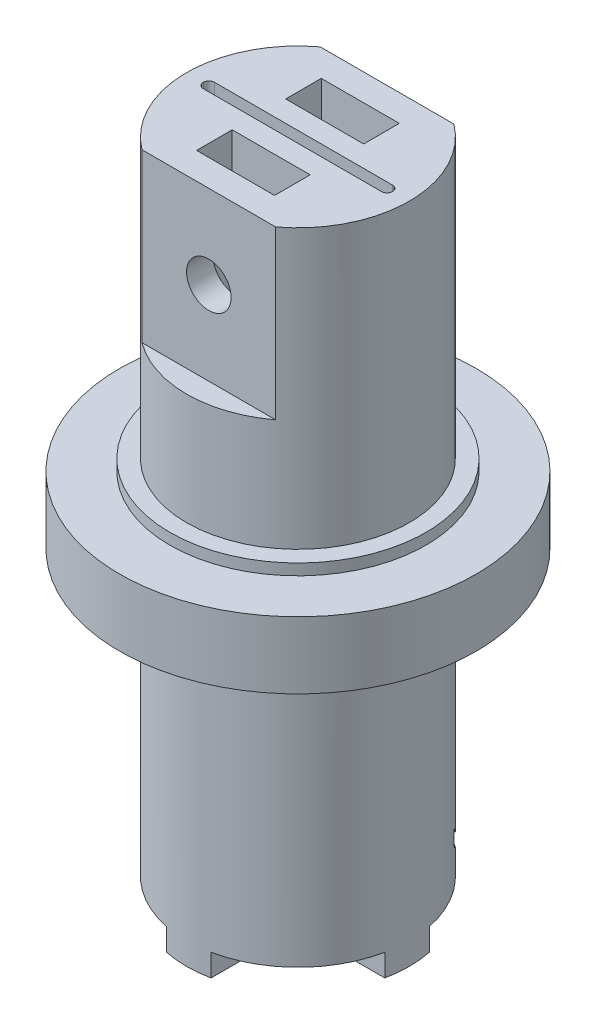
SolidWorks part; units mm, degrees
other "标注1"
sketch "草图8"
ref_plane "前视基准面" through (0, 0, 0) normal (0, 0, 1) x (1, 0, 0)
ref_plane "上视基准面" through (0, 0, 0) normal (0, 1, 0) x (1, 0, 0)
ref_plane "右视基准面" through (0, 0, 0) normal (1, 0, 0) x (0, 0, -1)
sketch "草图1" plane through (0, 0, 0) normal (0, 0, 1) x (1, 0, 0)
  line L0 (5, 2.5) -> (5, 60)
  line L1 (5, 2.5) -> (-5, 2.5)
  line L2 (-5, 2.5) -> (-5, 28)
  line L3 (-5, 28) -> (-11, 28)
  line L4 (-11, 28) -> (-11, 34)
  line L7 (-5, 60) -> (5, 60)
  line L11 (-5, 60) -> (-5, 35)
  line L16 (-5, 35) -> (-6.5, 35)
  line L17 (-6.5, 35) -> (-6.5, 34)
  line L18 (-6.5, 34) -> (-11, 34)
revolve "旋转1" add sketch "草图1" angle 360 about L0
sketch "草图2" plane through (0, 60, 0) normal (0, 1, 0) x (1, 0, 0)
  line L0 (-3.5, 0.5) -> (13.5, 0.5)
  line L1 (13.5, 0.5) -> (13.5, -0.5)
  line L2 (13.5, -0.5) -> (-3.5, -0.5)
  line L3 (-3.5, -0.5) -> (-3.5, 0.5)
  line L4 (-3.5, 0.5) -> (13.5, -0.5) construction
  line L5 (13.5, 0.5) -> (-3.5, -0.5) construction
extrude "切除-拉伸1" cut sketch "草图2" against normal blind 26
fillet "圆角1" radius 0.5 4 edges at (-3.5, 47, 0.5) (-3.5, 47, -0.5) (13.5, 47, 0.5) (13.5, 47, -0.5)
sketch "草图3" plane through (0, 60, 0) normal (0, 1, 0) x (1, 0, 0)
  line L2 (5, -8) -> (11, -8)
  line L3 (5, -8) -> (-1, -8)
  line L4 (5, 8) -> (11, 8)
  line L5 (5, 8) -> (-1, 8)
  arc A0 (-1, -8) -> (11, -8) centre (5, 0) ccw
  circle A1 centre (5, 0) radius 10
  arc A2 (11, 8) -> (-1, 8) centre (5, 0) ccw
  dimension "D1" = 0
extrude "切除-拉伸2" cut sketch "草图3" against normal blind 15
sketch "草图4" plane through (0, 60, 0) normal (0, 1, 0) x (1, 0, 0)
  line L0 (5, 0) -> (5, 4) construction
  line L1 (5, 0) -> (5, -4) construction
  line L2 (1.5, -2.4) -> (1.5, -4)
  line L3 (1.5, 4) -> (1.5, 2.4)
  line L4 (1.5, 2.4) -> (8.5, 2.4)
  line L5 (8.5, 2.4) -> (8.5, 5.6)
  line L6 (8.5, 5.6) -> (1.5, 5.6)
  line L7 (1.5, 5.6) -> (1.5, 4)
  line L8 (8.5, -5.6) -> (8.5, -2.4)
  line L9 (1.5, -5.6) -> (8.5, -5.6)
  line L10 (8.5, -2.4) -> (1.5, -2.4)
  line L11 (1.5, -4) -> (1.5, -5.6)
extrude "切除-拉伸3" cut sketch "草图4" against normal blind 15
sketch "草图5" plane through (0, 0, -8) normal (0, 0, -1) x (-1, 0, 0)
  line L0 (-11, 52.5) -> (-5, 52.5) construction
  line L1 (-5, 52.5) -> (-5, 60) construction
  circle A0 centre (-5, 52.5) radius 2
extrude "切除-拉伸4" cut sketch "草图5" against normal blind 17
sketch "草图6" plane through (0, 2.5, 0) normal (0, -1, 0) x (1, 0, 0)
  line L0 (7, 2) -> (14.798, 2)
  line L1 (7, -2) -> (14.798, -2)
  line L2 (3, -2) -> (-4.798, -2)
  line L3 (3, 2) -> (-4.798, 2)
  line L4 (7, -2) -> (7, -9.798)
  line L5 (3, -2) -> (3, -9.798)
  line L6 (7, 2) -> (7, 9.798)
  line L7 (3, 2) -> (3, 9.798)
  circle A0 centre (5, 0) radius 2 construction
  circle A1 centre (5, 0) radius 10
  arc A2 (7, 9.798) -> (3, 9.798) centre (5, 0) ccw
  arc A3 (-4.798, 2) -> (-4.798, -2) centre (5, 0) ccw
  arc A4 (3, -9.798) -> (7, -9.798) centre (5, 0) ccw
  arc A5 (14.798, -2) -> (14.798, 2) centre (5, 0) ccw
  dimension "D1" = 0
extrude "凸台-拉伸1" add sketch "草图6" along normal blind 2
ref_plane "基准面1" through (5, 0, 0) normal (1, 0, 0) x (0, 0, -1)
sketch "草图7" plane through (5, 0, 0) normal (1, 0, 0) x (0, 0, -1)
  line L1 (10, 4.5102) -> (10, 3.5102)
  line L2 (16, 34) -> (-16, 34) construction
  line L11 (0.5, 34) -> (-0.5, 34)
  ellipse E0 centre (10, 34) end of major axis (10, 64.4898) minor radius 10.5 (-0.5, 34) -> (10, 3.5102) ccw
  ellipse E1 centre (10, 34) end of major axis (10, 63.4898) minor radius 9.5 (0.5, 34) -> (10, 4.5102) ccw
extrude "切除-拉伸5" cut sketch "草图7" against normal blind 8 and the other way blind 8
